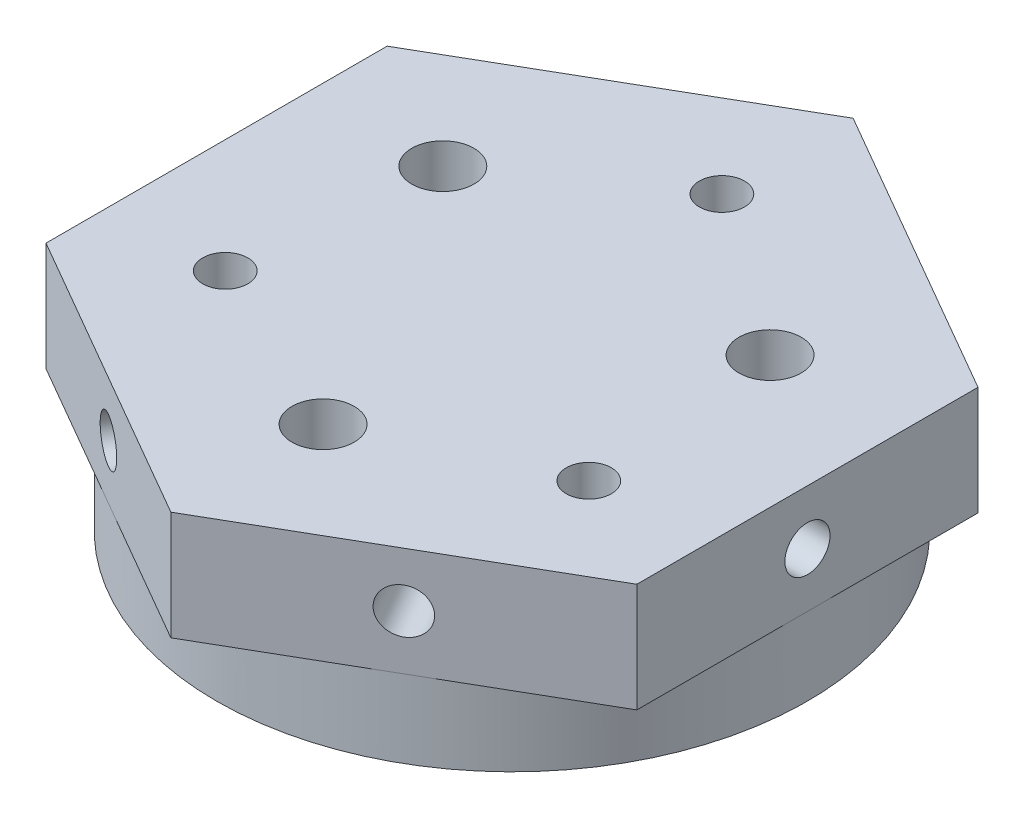
SolidWorks part; units mm, degrees
ref_plane "前视基准面" through (0, 0, 0) normal (0, 0, 1) x (1, 0, 0)
ref_plane "上视基准面" through (0, 0, 0) normal (0, 1, 0) x (1, 0, 0)
ref_plane "右视基准面" through (0, 0, 0) normal (1, 0, 0) x (0, 0, -1)
sketch "草图1" plane through (0, 0, 0) normal (0, 1, 0) x (1, 0, 0)
  line L0 (0, 0) -> (0, 33.3478) construction
  line L1 (0, 0) -> (11.2563, 0) construction
  line L2 (-11.6913, -6.75) -> (0, 0) construction
  line L3 (0, 0) -> (11.6913, -6.75) construction
  line L4 (0, 0) -> (-10.5222, 6.075) construction
  line L5 (10.5222, 6.075) -> (0, 0) construction
  circle A0 centre (0, 0) radius 19
  circle A1 centre (0, 13.5) radius 1.45
  circle A2 centre (0, 0) radius 13.5 construction
  circle A3 centre (-11.6913, -6.75) radius 1.45
  circle A4 centre (11.6913, -6.75) radius 1.45
  circle A5 centre (0, 0) radius 12.15 construction
  circle A6 centre (-10.5222, 6.075) radius 2
  circle A7 centre (0, -12.15) radius 2
  circle A8 centre (10.5222, 6.075) radius 2
  dimension "D1" = 38
  dimension "D2" = 27
  dimension "D3" = 2.9
  dimension "D6" = 24.3
  dimension "D8" = 4
  dimension "D4" = 120
  dimension "D5" = 120
  dimension "D7" = 60
  dimension "D9" = 60
extrude "凸台-拉伸1" add sketch "草图1" along normal blind 12
sketch "草图2" plane through (0, 12, 0) normal (0, 1, 0) x (1, 0, 0)
  line L0 (0, 21.9393) -> (0, 0) construction
  line L1 (0, 21.9393) -> (-19, 10.9697)
  line L2 (-19, 10.9697) -> (-19, -10.9697)
  line L3 (-19, -10.9697) -> (0, -21.9393)
  line L4 (0, -21.9393) -> (19, -10.9697)
  line L5 (19, -10.9697) -> (19, 10.9697)
  line L6 (19, 10.9697) -> (0, 21.9393)
  circle A0 centre (0, 0) radius 19 construction
  circle A1 centre (0, 13.5) radius 1.45
  circle A2 centre (0, 13.5) radius 1.45 construction
  circle A3 centre (-10.5222, 6.075) radius 2
  circle A4 centre (-10.5222, 6.075) radius 2 construction
  circle A5 centre (10.5222, 6.075) radius 2
  circle A6 centre (10.5222, 6.075) radius 2 construction
  circle A7 centre (-11.6913, -6.75) radius 1.45
  circle A8 centre (-11.6913, -6.75) radius 1.45 construction
  circle A9 centre (0, -12.15) radius 2
  circle A10 centre (0, -12.15) radius 2 construction
  circle A11 centre (11.6913, -6.75) radius 1.45
  circle A12 centre (11.6913, -6.75) radius 1.45 construction
  dimension "D1" = 38
extrude "凸台-拉伸2" add sketch "草图2" against normal blind 7
sketch "草图3" plane through (9.5, 0, 16.4545) normal (0.5, 0, 0.866) x (0.866, 0, -0.5)
  line L1 (0, 12) -> (0, 5) construction
  line L2 (-10.9697, 12) -> (10.9697, 12) construction
  circle A1 centre (0, 8.5) radius 1.45
  dimension "D1" = 2.9
extrude "切除-拉伸1" cut sketch "草图3" against normal blind 8
sketch "草图4" plane through (-9.5, 0, 16.4545) normal (-0.5, 0, 0.866) x (0.866, 0, 0.5)
  line L0 (0, 5) -> (0, 12) construction
  line L1 (-10.9697, 12) -> (10.9697, 12) construction
  circle A0 centre (0, 8.5) radius 1.45
  dimension "D1" = 2.9
extrude "切除-拉伸2" cut sketch "草图4" against normal blind 8
sketch "草图5" plane through (-19, 0, 0) normal (-1, 0, 0) x (0, 0, 1)
  line L0 (0, 5) -> (0, 12) construction
  line L1 (-10.9697, 12) -> (10.9697, 12) construction
  circle A0 centre (0, 8.5) radius 1.45
  dimension "D1" = 2.9
extrude "切除-拉伸3" cut sketch "草图5" against normal blind 8
sketch "草图6" plane through (19, 0, 0) normal (1, 0, 0) x (0, 0, -1)
  line L0 (0, 12) -> (0, 5) construction
  line L1 (-10.9697, 12) -> (10.9697, 12) construction
  circle A0 centre (0, 8.5) radius 1.45
  dimension "D1" = 2.9
extrude "切除-拉伸4" cut sketch "草图6" against normal blind 8
sketch "草图7" plane through (9.5, 0, -16.4545) normal (0.5, 0, -0.866) x (-0.866, 0, -0.5)
  line L0 (0, 12) -> (0, 5) construction
  line L1 (-10.9697, 12) -> (10.9697, 12) construction
  circle A0 centre (0, 8.5) radius 1.45
  dimension "D1" = 2.9
extrude "切除-拉伸5" cut sketch "草图7" against normal blind 8
